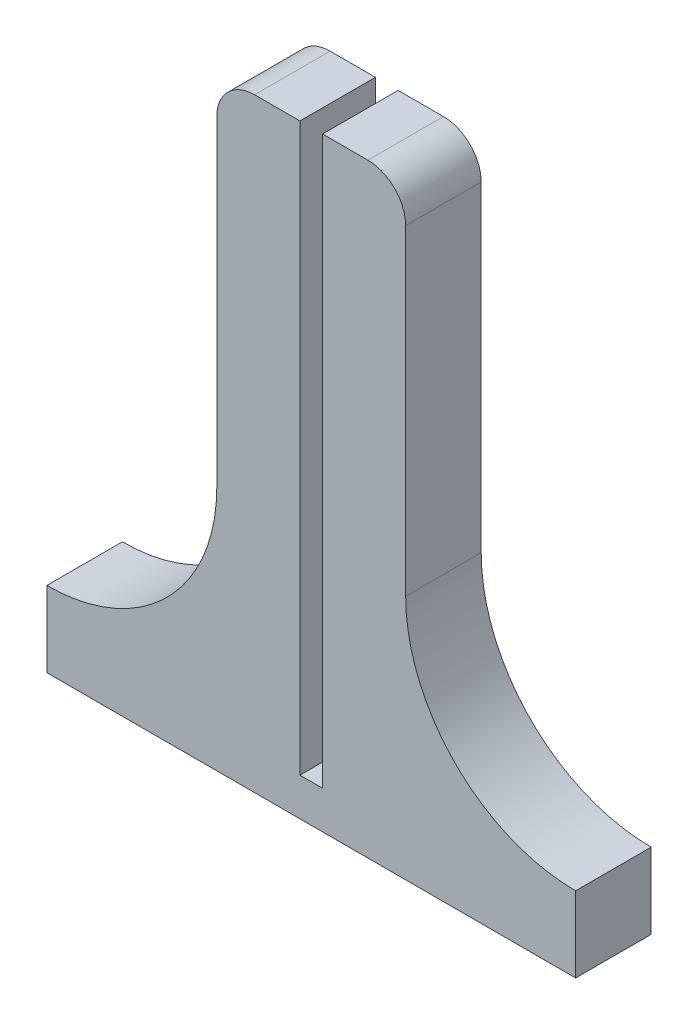
SolidWorks part; units mm, degrees
ref_plane "Plan de face" through (0, 0, 0) normal (0, 0, 1) x (1, 0, 0)
ref_plane "Plan de dessus" through (0, 0, 0) normal (0, 1, 0) x (1, 0, 0)
ref_plane "Plan de droite" through (0, 0, 0) normal (1, 0, 0) x (0, 0, -1)
sketch "Esquisse1" plane through (0, 0, 0) normal (0, 0, 1) x (1, 0, 0)
  line L0 (-70, 0) -> (70, 0)
  line L1 (70, 0) -> (70, 20)
  line L2 (25, 65) -> (25, 160)
  line L3 (25, 160) -> (-25, 160)
  line L4 (0, -36.4078) -> (0, 122.8519) construction
  line L5 (-70, 0) -> (-70, 20)
  line L6 (-25, 65) -> (-25, 160)
  arc A0 (70, 20) -> (25, 65) centre (70, 65) cw
  arc A1 (-70, 20) -> (-25, 65) centre (-70, 65) ccw
  point P4 (0, 0)
  point P15 (0, 160)
  dimension "D1" = 140
  dimension "D2" = 20
  dimension "D3" = 50
  dimension "D4" = 160
extrude "Boss.-Extru.1" add sketch "Esquisse1" along normal blind 20
fillet "Congé1" radius 10 2 edges at (-25, 160, 10) (25, 160, 10)
sketch "Esquisse2" plane through (0, 0, 20) normal (0, 0, 1) x (1, 0, 0)
  line L0 (-3, 10) -> (-3, 160)
  line L1 (-3, 10) -> (3, 10)
  line L2 (-3, 160) -> (3, 160)
  line L3 (3, 10) -> (3, 160)
  line L4 (-3, 10) -> (3, 160) construction
  line L5 (-3, 160) -> (3, 10) construction
  line L6 (-70, 0) -> (70, 0) construction
  line L7 (15, 160) -> (-15, 160) construction
  point P1 (0, 85)
  point P2 (0, 10)
  dimension "D1" = 6
  dimension "D2" = 10
extrude "Enlèv. mat.-Extru.1" cut sketch "Esquisse2" against normal blind 20
sketch "Esquisse3" plane through (-25, 0, 0) normal (-1, 0, 0) x (0, 0, 1)
  line L0 (10, 150) -> (10, 65) construction
  line L1 (20, 150) -> (0, 150) construction
  line L2 (20, 65) -> (0, 65) construction
  text T0 "Aïe Lab" font "Calibri" height in points 22
  point P7 (10, 65)
extrude "Enlèv. mat.-Extru.2" cut sketch "Esquisse3" against normal blind 0.6
